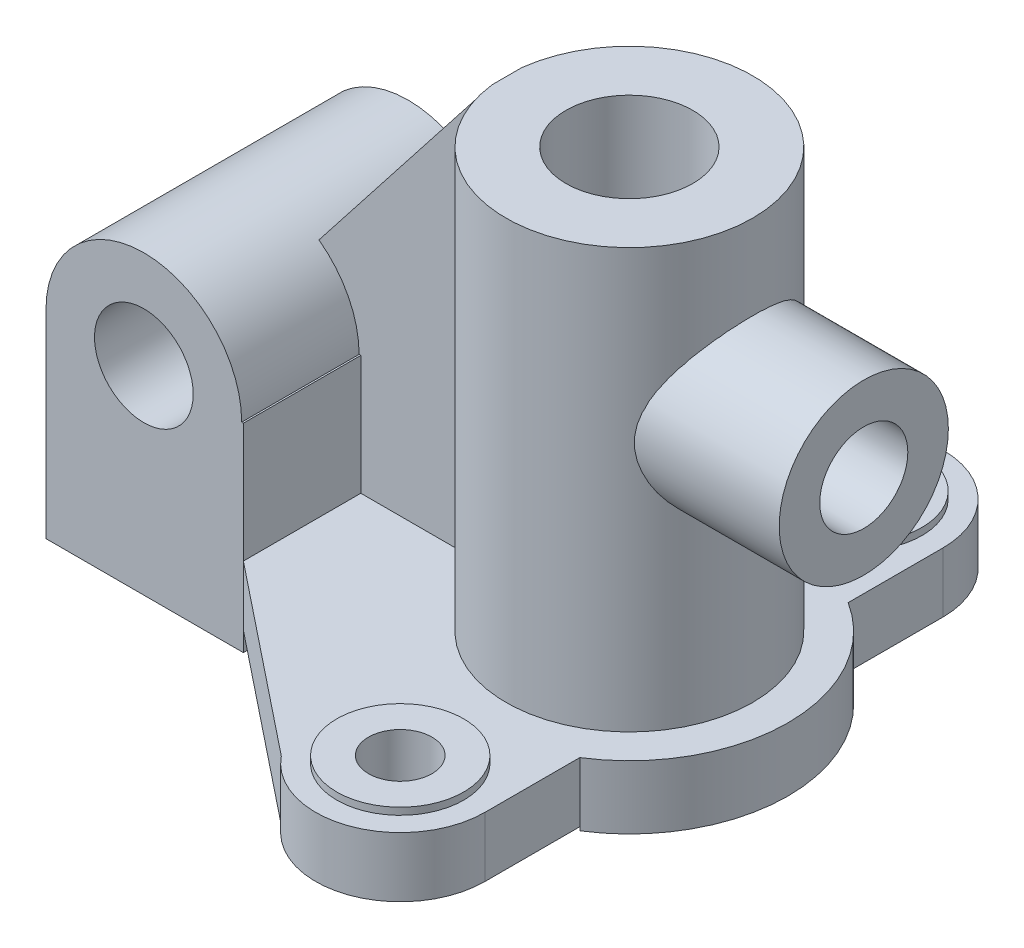
SolidWorks part; units mm, degrees
ref_plane "Front Plane" through (0, 0, 0) normal (0, 0, 1) x (1, 0, 0)
ref_plane "Top Plane" through (0, 0, 0) normal (0, 1, 0) x (1, 0, 0)
ref_plane "Right Plane" through (0, 0, 0) normal (1, 0, 0) x (0, 0, -1)
sketch "Sketch1" plane through (0, 0, 0) normal (0, 1, 0) x (1, 0, 0)
  line L1 (-28, 37.5) -> (28, 37.5)
  line L2 (-28, 37.5) -> (-28, -37.5)
  line L3 (-28, -37.5) -> (28, -37.5)
  line L5 (-28, 37.5) -> (28, -37.5) construction
  line L6 (-28, -37.5) -> (28, 37.5) construction
  line L9 (28, 37.5) -> (84.8809, 83.639)
  line L10 (28, -37.5) -> (81.2972, -80.0401)
  line L11 (124, 65) -> (124, -65)
  arc A0 (124, 65) -> (84.8809, 83.639) centre (100, 65) ccw
  arc A1 (81.2972, -80.0401) -> (124, -65) centre (100, -65) ccw
  point P0 (0, 0)
  dimension "D6" = 48
  dimension "D7" = 48
  dimension "D1" = 75
  dimension "D2" = 56
extrude "Boss-Extrude1" add sketch "Sketch1" along normal blind 17 contours L10 A1 L11 A0 L9 L1 L2 L3
sketch "Sketch2" plane through (0, 17, 0) normal (0, 1, 0) x (1, 0, 0)
  line L0 (-28, 37.5) -> (28, 37.5) construction
  line L1 (-28, 37.5) -> (28, 37.5)
  line L2 (-28, 37.5) -> (-28, -37.5)
  line L3 (-28, -37.5) -> (28, -37.5)
  line L4 (28, 37.5) -> (28, -37.5)
extrude "Boss-Extrude2" add sketch "Sketch2" against normal blind 22.5 contours L3 L4 L1 L2
sketch "Sketch3" plane through (0, 17, 0) normal (0, 1, 0) x (1, 0, 0)
  circle A0 centre (100, 65) radius 18
  dimension "D1" = 36
extrude "Boss-Extrude3" add sketch "Sketch3" along normal blind 2 contours A0
sketch "Sketch5" plane through (0, 17, 0) normal (0, 1, 0) x (1, 0, 0)
  circle A0 centre (100, -65) radius 18
  dimension "D1" = 36
extrude "Boss-Extrude4" add sketch "Sketch5" along normal blind 2 contours A0
sketch "Sketch6" plane through (0, 19, 0) normal (0, 1, 0) x (1, 0, 0)
  circle A0 centre (100, -65) radius 9
  dimension "D1" = 18
extrude "Cut-Extrude1" cut sketch "Sketch6" against normal blind 60 contours A0
sketch "Sketch7" plane through (0, 19, 0) normal (0, 1, 0) x (1, 0, 0)
  circle A0 centre (100, 65) radius 9
  dimension "D1" = 18
extrude "Cut-Extrude2" cut sketch "Sketch7" against normal blind 60 contours A0
sketch "Sketch10" plane through (0, 17, 0) normal (0, 1, 0) x (1, 0, 0)
  line L0 (109, 65) -> (137.6682, 65)
  line L1 (124, 38.0657) -> (124, -38.0657)
  line L4 (124, 65) -> (124, -65) construction
  circle A1 centre (100, 65) radius 9 construction
  arc A2 (124, -38.0657) -> (124, 38.0657) centre (100, 0) ccw
  dimension "D1" = 90
extrude "Boss-Extrude5" add sketch "Sketch10" against normal blind 18 contours A2 L1
sketch "Sketch11" plane through (0, 17, 0) normal (0, 1, 0) x (1, 0, 0)
  circle A0 centre (100, 0) radius 35
  dimension "D1" = 70
extrude "Boss-Extrude6" add sketch "Sketch11" along normal blind 119 contours A0
sketch "Sketch12" plane through (0, 136, 0) normal (0, 1, 0) x (1, 0, 0)
  circle A0 centre (100, 0) radius 18
  dimension "D1" = 36
extrude "Cut-Extrude3" cut sketch "Sketch12" against normal blind 119 contours A0
sketch "Sketch13" plane through (0, 136, 0) normal (0, 1, 0) x (1, 0, 0)
  line L0 (100, 0) -> (100, -35)
  line L1 (100, 0) -> (135, 0)
  circle A0 centre (100, 0) radius 35 construction
ref_plane "Plane1" through (135, 136, 0) normal (1, 0, 0) x (0, 0, -1)
sketch "Sketch16" plane through (135, 136, 0) normal (1, 0, 0) x (0, 0, -1)
  circle A0 centre (0, -48) radius 24
  dimension "D1" = 48
  dimension "D2" = 89
extrude "Boss-Extrude9" add sketch "Sketch16" along normal mid plane 63 separate body contours A0
sketch "Sketch17" plane through (166.5, 0, 0) normal (1, 0, 0) x (0, 0, -1)
  circle A0 centre (0, 88) radius 12.5
  dimension "D1" = 25
extrude "Cut-Extrude4" cut sketch "Sketch17" against normal blind 23 contours A0
sketch "Sketch18" plane through (166.5, 0, 0) normal (1, 0, 0) x (0, 0, -1)
  circle A0 centre (0, 88) radius 12.5
extrude "Cut-Extrude5" cut sketch "Sketch18" against normal blind 23 contours A0 rebuild error yes
sketch "Sketch22" plane through (0, 17, 0) normal (0, 1, 0) x (1, 0, 0)
  line L0 (-28, 37.5) -> (-28, -37.5) construction
  line L1 (-28, -4.1874) -> (65.2747, -4.1874)
  line L2 (-28, -4.1874) -> (-28, 4.3767)
  line L3 (-28, 4.3767) -> (65.2747, 4.3767)
  line L4 (65.2747, -4.1874) -> (65.2747, 4.3767)
  circle A0 centre (100, 0) radius 35 construction
extrude "Boss-Extrude10" add sketch "Sketch22" along normal blind 119 contours L1 L4 L3 L2
sketch "Sketch23" plane through (0, 0, 4.1874) normal (0, 0, 1) x (1, 0, 0)
  line L0 (-28, 17) -> (65.2514, 136)
  line L1 (65.2514, 136) -> (-28, 136)
  line L2 (-28, 136) -> (-28, 17) construction
  line L3 (-28, 136) -> (65.2514, 136) construction
  line L4 (-28, 136) -> (-28, 17)
extrude "Cut-Extrude6" cut sketch "Sketch23" against normal blind 119 contours L1 L4 L0
sketch "Sketch24" plane through (0, 17, 0) normal (0, 1, 0) x (1, 0, 0)
  line L1 (-28, -37.5) -> (27.5203, -37.5)
  line L2 (-28, -37.5) -> (-28, -20.3595)
  line L3 (-28, -20.3595) -> (27.5203, -20.3595)
  line L4 (27.5203, -37.5) -> (27.5203, -20.3595)
extrude "Boss-Extrude11" add sketch "Sketch24" along normal blind 1 contours L1 L4 L3 L2
sketch "Sketch25" plane through (0, 0, 37.5) normal (0, 0, 1) x (1, 0, 0)
  line L0 (-28, 50.883) -> (27.5203, 50.883)
  line L1 (-28, 18) -> (-28, -5.5) construction
  line L2 (27.5203, 18) -> (27.5203, 17) construction
  line L4 (-28, -5.5) -> (28, -5.5) construction
  arc A4 (27.5203, 50.883) -> (-28, 50.883) centre (-0.2398, 50.883) ccw
  point P1 (0, 0)
  point P4 (-29.4665, 51.1706)
  point P5 (-28.3899, 50.7668)
  point P6 (-28, 50.9463)
  point P9 (0, 0)
  point P10 (0, 0)
  point P11 (0, 0)
  point P12 (27.5203, 50.883)
  dimension "D1" = 56.383
extrude "Boss-Extrude12" add sketch "Sketch25" against normal blind 75 contours A4 L0
sketch "Sketch28" plane through (0, 50.883, 0) normal (0, -1, 0) x (1, 0, 0)
  line L1 (-28, 37.5) -> (28, 37.5)
  line L2 (-28, 37.5) -> (-28, -37.5)
  line L3 (-28, -37.5) -> (28, -37.5)
  line L4 (28, 37.5) -> (28, -37.5)
extrude "Boss-Extrude13" add sketch "Sketch28" along normal blind 47 contours L1 L4 L3 L2
sketch "Sketch29" plane through (0, 0, 37.5) normal (0, 0, 1) x (1, 0, 0)
  circle A0 centre (-0.2398, 50.883) radius 14
  dimension "D1" = 28
extrude "Cut-Extrude7" cut sketch "Sketch29" against normal blind 120 contours A0
